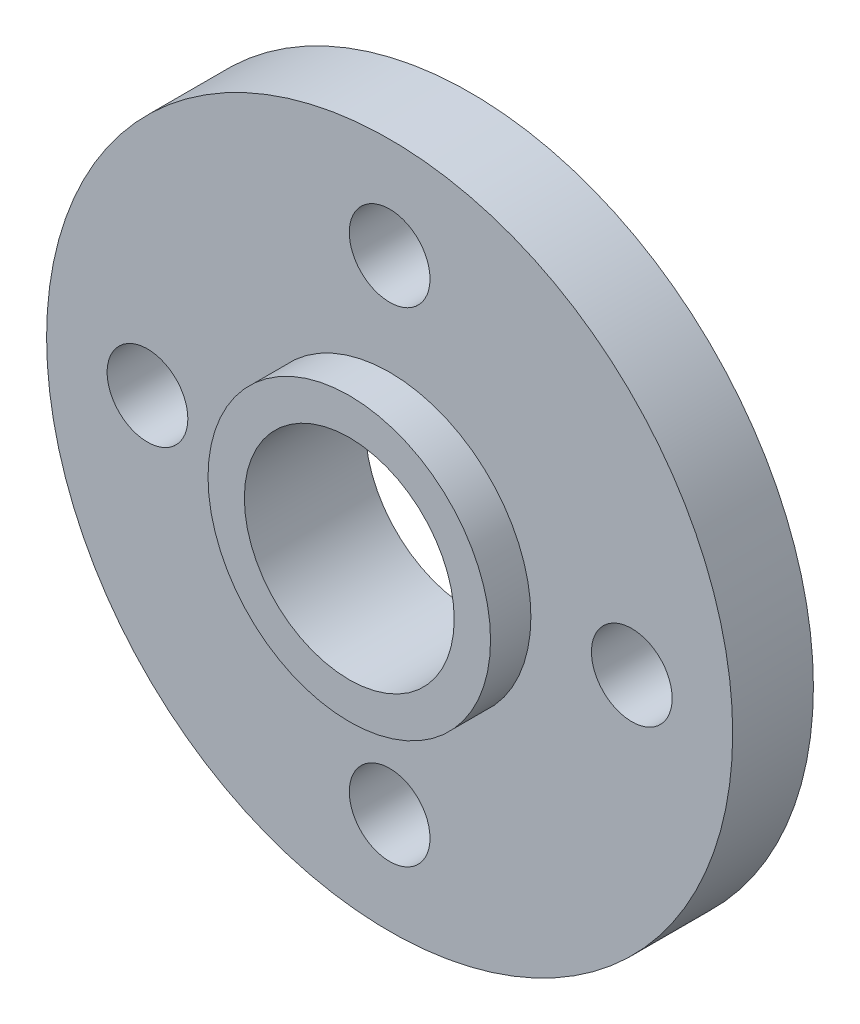
SolidWorks part; units mm, degrees
material "ABS"
ref_plane "Спереди" through (0, 0, 0) normal (0, 0, 1) x (1, 0, 0)
ref_plane "Сверху" through (0, 0, 0) normal (0, 1, 0) x (1, 0, 0)
ref_plane "Справа" through (0, 0, 0) normal (1, 0, 0) x (0, 0, -1)
sketch "Эскиз2" plane through (0, 0, 0) normal (0, 0, 1) x (1, 0, 0)
  line L0 (0, 0) -> (-8.5, 0) construction
  circle A0 centre (0, 0) radius 2.6
  circle A1 centre (0, 0) radius 8.5
  circle A2 centre (-6, 0) radius 1
  circle A3 centre (0, 6) radius 1
  circle A4 centre (6, 0) radius 1
  circle A5 centre (0, -6) radius 1
  point P16 (0, 0)
  dimension "D1" = 17
  dimension "D2" = 5.2
  dimension "D3" = 2
  dimension "D4" = 6
  dimension "D5" = 4
extrude "Бобышка-Вытянуть1" add sketch "Эскиз2" along normal blind 2
sketch "Эскиз3" plane through (0, 0, 2) normal (0, 0, 1) x (1, 0, 0)
  circle A0 centre (0, 0) radius 2.6
  circle A1 centre (0, 0) radius 3.5
  dimension "D1" = 7
  dimension "D2" = 5.2
extrude "Бобышка-Вытянуть2" add sketch "Эскиз3" along normal blind 1
